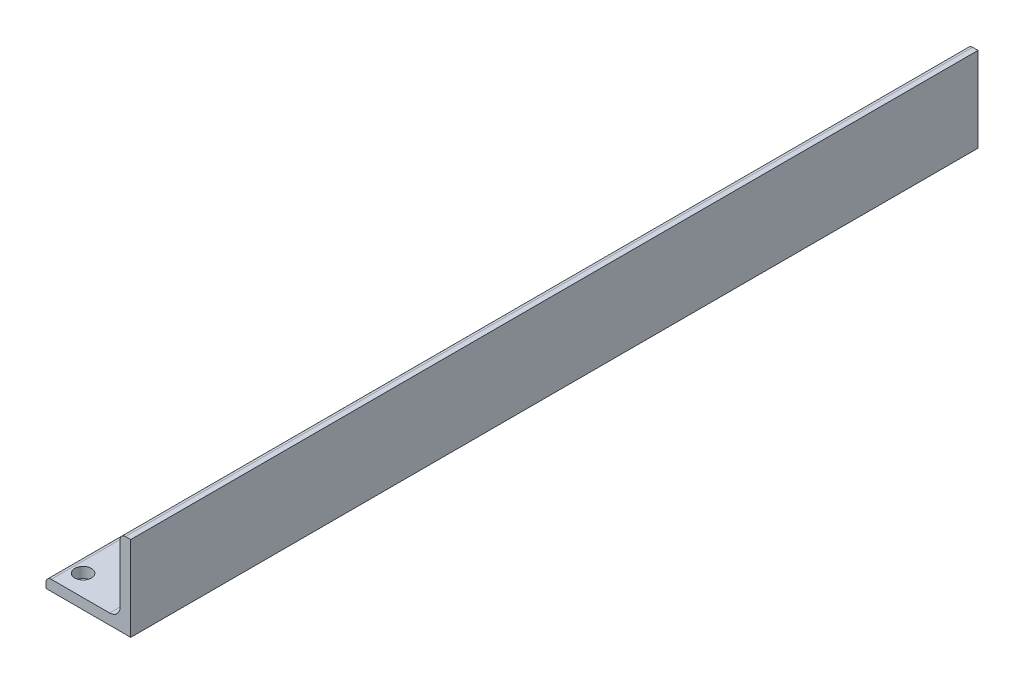
SolidWorks part; units mm, degrees
ref_plane "Front Plane" through (0, 0, 0) normal (0, 0, 1) x (1, 0, 0)
ref_plane "Top Plane" through (0, 0, 0) normal (0, 1, 0) x (1, 0, 0)
ref_plane "Right Plane" through (0, 0, 0) normal (1, 0, 0) x (0, 0, -1)
sketch "Sketch0" plane through (0, 0, 0) normal (0, 0, 1) x (1, 0, 0)
  line L0 (-12.7, -12.7) -> (12.7, -12.7)
  line L1 (12.7, -12.7) -> (12.7, 12.7)
  line L2 (12.7, 0) -> (0, 0) construction
  line L3 (0, 0) -> (0, -12.7) construction
  line L4 (9.525, -6.35) -> (9.525, 12.7) construction
  line L5 (6.35, -9.525) -> (-12.7, -9.525) construction
  arc A0 (9.525, -6.35) -> (6.35, -9.525) centre (6.35, -6.35) cw
  point P3 (8.5951, -8.5951)
  dimension "Inside Corner Radius" = 3.175
  dimension "Outside Height" = 25.4
  dimension "Inside Height" = 22.225
  dimension "Inside Width" = 22.225
  dimension "Wall Thickness" = 3.175
  dimension "D1" = 3.175
  dimension "Outside Width" = 25.4
sketch "Sketch1" plane through (0, 0, 0) normal (1, 0, 0) x (0, 0, -1)
  line L0 (304.8, 0) -> (-304.8, 0)
  point P4 (0, 0)
  dimension "Length" = 609.6
sketch "Sketch2" plane through (0, 0, 0) normal (0, 0, 1) x (1, 0, 0)
  line L0 (-12.7, -12.7) -> (12.7, -12.7)
  line L1 (12.7, -12.7) -> (12.7, 12.7)
  line L2 (12.7, 12.7) -> (9.525, 12.7) construction
  line L3 (9.525, 11.1125) -> (9.525, -6.35)
  line L4 (6.35, -9.525) -> (-11.1125, -9.525)
  line L5 (-12.7, -12.7) -> (-12.7, -9.525) construction
  line L6 (11.1125, 12.7) -> (12.7, 12.7)
  line L7 (-12.7, -11.1125) -> (-12.7, -12.7)
  line L8 (12.7, 0) -> (0, 0) construction
  line L9 (0, 0) -> (0, -12.7) construction
  arc A0 (9.525, 11.1125) -> (11.1125, 12.7) centre (11.1125, 11.1125) cw
  arc A1 (-12.7, -11.1125) -> (-11.1125, -9.525) centre (-11.1125, -11.1125) cw
  arc A2 (9.525, -6.35) -> (6.35, -9.525) centre (6.35, -6.35) cw
  dimension "Inside Radius" = 3.175
  dimension "Height" = 25.4
  dimension "Width" = 25.4
  dimension "Thickness" = 3.175
extrude "Boss-Extrude1" add sketch "Sketch2" along normal mid plane 609.6
sketch "Break Locations" plane through (0, 0, 0) normal (1, 0, 0) x (0, 0, -1)
  line L0 (-278.892, 0) -> (278.892, 0)
  line L1 (-304.8, -12.7) -> (-304.8, 12.7) construction
  line L2 (304.8, -12.7) -> (304.8, 12.7) construction
  point P0 (-283.21, 0)
  point P1 (283.21, 0)
  point P10 (0, 0)
  point P11 (278.892, 0)
  point P13 (-278.892, 0)
  dimension "D1" = 21.59
  dimension "D2" = 21.59
  dimension "D3" = 25.908
sketch "Sketch7" plane through (0, -12.7, 0) normal (0, -1, 0) x (1, 0, 0)
  line L0 (-12.7, -50.8) -> (12.7, -50.8)
  line L1 (-12.7, 304.8) -> (12.7, 304.8)
  line L2 (-12.7, 304.8) -> (-12.7, -304.8)
  line L3 (-12.7, -304.8) -> (12.7, -304.8)
  line L4 (12.7, 304.8) -> (12.7, -304.8)
  line M4 (12.7, -304.8) -> (12.7, 304.8)
  line M5 (12.7, 304.8) -> (-12.7, 304.8)
  line M6 (-12.7, 304.8) -> (-12.7, -304.8)
  dimension "D1" = 254
extrude "Cut-Extrude1" cut sketch "Sketch7" against normal blind 254 contours L0 M6 M4 M5 region at (0, -12.7, 127)
sketch "Sketch3" plane through (0, 0, 0) normal (0, 1, 0) x (1, 0, 0)
  line L2 (12.7, 50.8) -> (12.7, 304.8) construction
  line L3 (6.35, 304.8) -> (-11.1125, 304.8) construction
  line L4 (-11.1125, 177.8) -> (6.35, 177.8) construction
  line L5 (-11.1125, 50.8) -> (-11.1125, 304.8) construction
  line L6 (6.35, 50.8) -> (6.35, 304.8) construction
  line L7 (4.7625, 273.05) -> (4.7625, 234.95) construction
  line L8 (-1.5875, 304.8) -> (-1.5875, 177.8) construction
  circle A2 centre (4.7625, 273.05) radius 2.5
  circle A3 centre (4.7625, 234.95) radius 2.5
  circle A4 centre (4.7625, 196.85) radius 2.5
  circle A5 centre (4.7625, 158.75) radius 2.5
  circle A6 centre (4.7625, 120.65) radius 2.5
  circle A7 centre (4.7625, 82.55) radius 2.5
  circle A8 centre (4.7625, 44.45) radius 2.5
  circle A9 centre (4.7625, 6.35) radius 2.5
  circle A10 centre (4.7625, -31.75) radius 2.5
  circle A11 centre (4.7625, -69.85) radius 2.5
  circle A12 centre (4.7625, -107.95) radius 2.5
  circle A15 centre (-7.9375, -107.95) radius 2.5
  circle A16 centre (-7.9375, -69.85) radius 2.5
  circle A17 centre (-7.9375, -31.75) radius 2.5
  circle A18 centre (-7.9375, 6.35) radius 2.5
  circle A19 centre (-7.9375, 44.45) radius 2.5
  circle A20 centre (-7.9375, 82.55) radius 2.5
  circle A21 centre (-7.9375, 120.65) radius 2.5
  circle A22 centre (-7.9375, 158.75) radius 2.5
  circle A23 centre (-7.9375, 196.85) radius 2.5
  circle A24 centre (-7.9375, 234.95) radius 2.5
  circle A25 centre (-7.9375, 273.05) radius 2.5
  circle A26 centre (-7.9375, 298.45) radius 2.5
  circle A27 centre (-7.9375, 57.15) radius 2.5
  dimension "D3" = 25.4
  dimension "D1" = 5
  dimension "D2" = 12.7
  dimension "D6" = 7.9375
  dimension "D7" = 31.75
  dimension "D9" = 38.1
  dimension "D8" = 11
extrude "Cut-Extrude2" cut sketch "Sketch3" against normal blind 254
sketch "Sketch8" plane through (12.7, 0, -12.7) normal (-1, 0, 0) x (0, 0, 1)
  line L0 (-38.1, -6.35) -> (-292.1, -6.35) construction
  line L1 (-38.1, 11.1125) -> (-292.1, 11.1125) construction
  line L2 (-38.1, -12.7) -> (-292.1, -12.7) construction
  line L3 (-292.1, 11.1125) -> (-292.1, -6.35) construction
  line L4 (-165.1, 11.1125) -> (-165.1, -6.35) construction
  line L7 (25.4, -3.175) -> (-12.7, -3.175) construction
  circle A0 centre (-53.975, 6.35) radius 2.5
  circle A1 centre (-47.625, 0) radius 2.5
  circle A2 centre (25.4, -3.175) radius 2.5
  circle A3 centre (-12.7, -3.175) radius 2.5
  circle A4 centre (-50.8, -3.175) radius 2.5
  circle A5 centre (-88.9, -3.175) radius 2.5
  circle A6 centre (-127, -3.175) radius 2.5
  circle A7 centre (-165.1, -3.175) radius 2.5
  circle A8 centre (-203.2, -3.175) radius 2.5
  circle A9 centre (-241.3, -3.175) radius 2.5
  circle A10 centre (-279.4, -3.175) radius 2.5
  circle A11 centre (-317.5, -3.175) radius 2.5
  circle A12 centre (-355.6, -3.175) radius 2.5
  circle A13 centre (-282.575, 0) radius 2.5
  circle A14 centre (-276.225, 6.35) radius 2.5
  dimension "D3" = 5
  dimension "D1" = 9.525
  dimension "D2" = 12.7
  dimension "D4" = 9.525
  dimension "D5" = 19.05
  dimension "D6" = 15.875
  dimension "D9" = 38.1
  dimension "D8" = 11
extrude "Cut-Extrude4" cut sketch "Sketch8" along normal blind 254 rebuild error yes
equation "\"D1@Break Locations\" = .85 * \"Height@Sketch2\""
equation "\"D2@Break Locations\"=\"D1@Break Locations\""
equation "\"Thickness@Sketch2\" = \"Wall Thickness@Sketch0\""
equation "\"Height@Sketch2\" = \"Outside Height@Sketch0\""
equation "\"Width@Sketch2\" = \"Outside Width@Sketch0\""
equation "\"Inside Radius@Sketch2\" = \"Inside Corner Radius@Sketch0\""
equation "\"Length@Boss-Extrude1\" = \"Length@Sketch1\""
equation "\"D3@Break Locations\"=\"D2@Break Locations\"*1.2"
equation "\"D1@Sketch0\"=\"Wall Thickness@Sketch0\""
